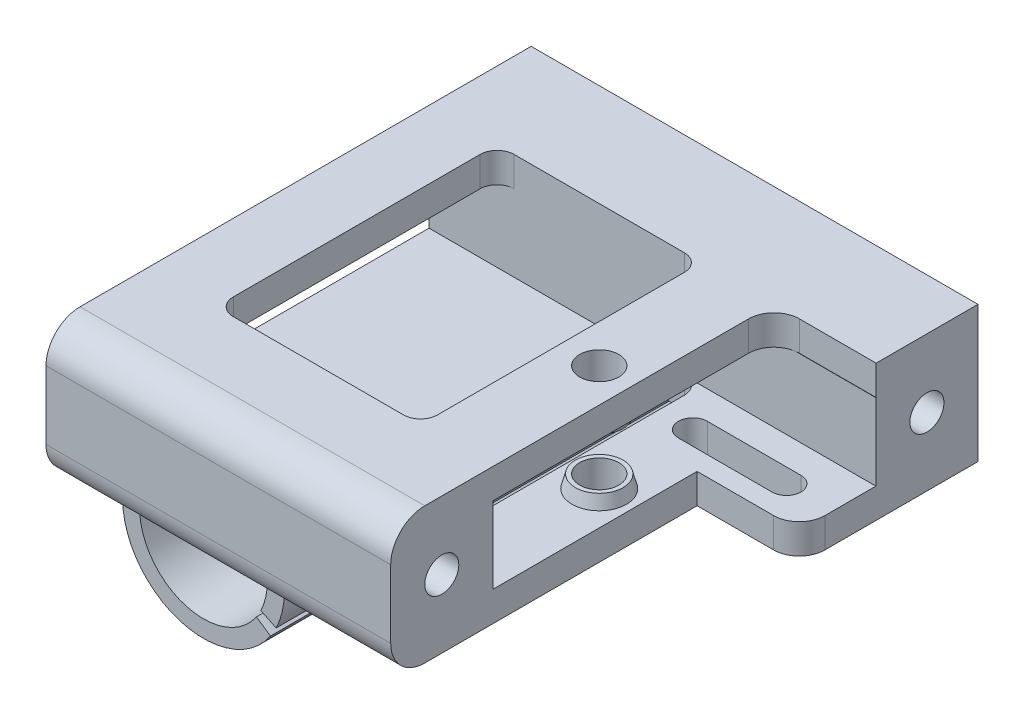
SolidWorks part; units mm, degrees
ref_plane "Front Plane" through (0, 0, 0) normal (0, 0, 1) x (1, 0, 0)
ref_plane "Top Plane" through (0, 0, 0) normal (0, 1, 0) x (1, 0, 0)
ref_plane "Right Plane" through (0, 0, 0) normal (1, 0, 0) x (0, 0, -1)
sketch "Sketch1" plane through (0, 0, 0) normal (0, 0, 1) x (1, 0, 0)
  line L0 (0, 0) -> (0, -31.5)
  line L1 (0, -31.5) -> (19, -31.5)
  line L2 (19, -31.5) -> (19, -16)
  line L3 (19, -16) -> (52.5, -16)
  line L4 (52.5, -16) -> (52.5, 0)
  line L5 (52.5, 0) -> (0, 0)
  line L6 (0, 0) -> (0.6966, -0.1385)
  dimension "D1" = 31.5
  dimension "D2" = 19
  dimension "D3" = 52.5
  dimension "D4" = 16
extrude "Boss-Extrude1" add sketch "Sketch1" along normal blind 57 contours L4 L5 L0 L1 L2 L3 region at (21.9019, -12.0885, 0)
ref_plane "Plane1" through (0, 0, 50) normal (0, 0, 1) x (1, 0, 0)
sketch "Sketch3" plane through (0, 0, 0) normal (-1, 0, 0) x (0, 0, 1)
  line L0 (57, 0) -> (0, 0) construction
  line L1 (12, -3.5) -> (45, -3.5)
  line L2 (12, -3.5) -> (12, -12.5)
  line L3 (12, -12.5) -> (45, -12.5)
  line L4 (45, -3.5) -> (45, -12.5)
  line L5 (57, -31.5) -> (48, -31.5)
  line L6 (57, -31.5) -> (57, -16)
  line L7 (57, -16) -> (48, -16)
  line L8 (48, -31.5) -> (48, -16)
  line L9 (0, 0) -> (0, -31.5) construction
  line L14 (57, -31.5) -> (0, -31.5) construction
  dimension "D1" = 9
  dimension "D2" = 33
  dimension "D3" = 3.5
  dimension "D4" = 12
  dimension "D5" = 15.5
  dimension "D6" = 9
extrude "Cut-Extrude2" cut sketch "Sketch3" against normal through all
fillet "Fillet1" radius 4 2 edges at (26.25, 0, 57) (26.25, -16, 57)
sketch "Sketch4" plane through (0, 0, 0) normal (0, 0, -1) x (-1, 0, 0)
  line L0 (-9.5, -22) -> (-9.5, -31.5) construction
  line L1 (0, -31.5) -> (-19, -31.5) construction
  line L2 (-15.7178, -26.1939) -> (-17.3759, -27.3123)
  line L3 (0, -31.5) -> (-19, -31.5)
  line L4 (0, -31.5) -> (0, -16)
  line L5 (0, -16) -> (-19, -16)
  line L6 (-19, -31.5) -> (-19, -16)
  line L7 (-16.241, -25.2878) -> (-18.0385, -26.1645)
  line L8 (-16.241, -25.2878) -> (-9.5, -22) construction
  circle A0 centre (-9.5, -22) radius 7.5
  circle A1 centre (-9.5, -22) radius 9.5
  line M8 (-19, -31.5) -> (0, -31.5)
  line M9 (0, -31.5) -> (0, 0)
  dimension "D1" = 15
  dimension "D2" = 19
  dimension "D3" = 8
  dimension "D4" = 64
extrude "Cut-Extrude3" cut sketch "Sketch4" against normal through all contours L5 A0 | L5 A0 | A1 L6 M8 | A1 L3 M9 | L7 A1 L2 A0 region at (16.8892, -26.2661, 0) region at (9.5, -22.3626, 0) region at (16.878, -29.378, 0) region at (2.122, -29.378, 0) region at (9.5, -15.3945, 0)
sketch "Sketch5" plane through (0, -16, 0) normal (0, -1, 0) x (1, 0, 0)
  line L0 (32, 28.5) -> (36, 28.5) construction
  line L1 (22, 45) -> (30, 45)
  line L2 (20, 43) -> (20, 14)
  line L3 (22, 12) -> (30, 12)
  line L4 (32, 43) -> (32, 14)
  line L5 (36, 17) -> (47, 17) construction
  line L6 (36, 18.7) -> (47, 18.7)
  line L7 (36, 15.3) -> (47, 15.3)
  line L8 (19, 48) -> (19, 0) construction
  line L9 (36, 28.5) -> (36, 17) construction
  line L10 (19, 0) -> (52.5, 0) construction
  line L11 (52.5, 0) -> (52.5, 18) construction
  line L12 (52.5, 53) -> (52.5, 0) construction
  line L14 (49.5, 18) -> (49.5, 21) construction
  line L15 (49.5, 21) -> (40.5, 21)
  line L16 (40.5, 21) -> (40.5, 57)
  line L17 (0, 57) -> (52.5, 57) construction
  line L18 (40.5, 57) -> (52.5, 57)
  line L19 (52.5, 57) -> (52.5, 18)
  arc A0 (20, 14) -> (22, 12) centre (22, 14) ccw
  arc A1 (30, 12) -> (32, 14) centre (30, 14) ccw
  arc A2 (32, 43) -> (30, 45) centre (30, 43) ccw
  arc A3 (22, 45) -> (20, 43) centre (22, 43) ccw
  circle A4 centre (36, 28.5) radius 2 construction
  arc A5 (36, 18.7) -> (36, 15.3) centre (36, 17) ccw
  arc A6 (47, 15.3) -> (47, 18.7) centre (47, 17) ccw
  arc A7 (52.5, 18) -> (49.5, 21) centre (49.5, 18) ccw
  point P17 (41.5, 17)
  line M7 (52.5, 53) -> (14, 53)
  line M12 (52.5, 0) -> (52.5, 53)
  dimension "D1" = 2
  dimension "D4" = 4
  dimension "D6" = 1.7
  dimension "D9" = 11.5
  dimension "D12" = 6
  dimension "D2" = 12
  dimension "D3" = 33
  dimension "D5" = 4
  dimension "D7" = 11
  dimension "D8" = 1
  dimension "D10" = 12
  dimension "D11" = 18
  dimension "D13" = 9
extrude "Cut-Extrude4" cut sketch "Sketch5" against normal up to surface (12.5 mm away) contours A4 | L7 A6 L6 A5 | A7 L16 L15 M12 M7 | L19 L18 L16 M7 | L2 A0 L3 A1 L4 A2 L1 A3 region at (41.5, -16, 17) region at (46.5267, -16, 36.9166) region at (46.5, -16, 55) up to face at (26.25, -3.5, 28.5)
sketch "Sketch6" plane through (0, 0, 0) normal (0, 1, 0) x (1, 0, 0)
  line L0 (52.5, 0) -> (0, 0) construction
  line L1 (10, -12) -> (30, -12)
  line L2 (8, -14) -> (8, -43)
  line L3 (10, -45) -> (30, -45)
  line L4 (32, -14) -> (32, -43)
  line L5 (0, -53) -> (0, 0) construction
  line L6 (52.5, -56.9686) -> (40.5, -56.9686) construction
  line L7 (43.5, -11.9686) -> (52.5, -11.9686)
  line L8 (40.5, -14.9686) -> (40.5, -56.9686)
  line L9 (40.5, -56.9686) -> (52.5, -56.9686)
  line L10 (52.5, -11.9686) -> (52.5, -56.9686)
  line L11 (52.5, -53) -> (52.5, 0) construction
  line L12 (36, -28.5) -> (32, -28.5) construction
  arc A0 (10, -45) -> (8, -43) centre (10, -43) cw
  arc A1 (32, -43) -> (30, -45) centre (30, -43) cw
  arc A2 (32, -14) -> (30, -12) centre (30, -14) ccw
  arc A3 (10, -12) -> (8, -14) centre (10, -14) ccw
  arc A4 (43.5, -11.9686) -> (40.5, -14.9686) centre (43.5, -14.9686) ccw
  circle A5 centre (36, -28.5) radius 2 construction
  point P6 (8, -45)
  point P11 (32, -12)
  point P14 (8, -12)
  point P25 (40.5, -11.9686)
  dimension "D3" = 2
  dimension "D8" = 3
  dimension "D9" = 4
  dimension "D10" = 4
  dimension "D1" = 33
  dimension "D2" = 24
  dimension "D4" = 12
  dimension "D5" = 8
  dimension "D6" = 45
  dimension "D7" = 12
extrude "Cut-Extrude5" cut sketch "Sketch6" against normal up to surface (3.5 mm away) up to face at (31, -3.5, 37.9895)
sketch "Sketch9" plane through (0, -3.5, 0) normal (0, -1, 0) x (1, 0, 0)
  line L0 (40.5, 21) -> (40.5, 53) construction
  line L1 (19, 0) -> (52.5, 0) construction
  circle A0 centre (36.5, 28.5) radius 3.2
  dimension "D1" = 6.4
  dimension "D2" = 4
  dimension "D3" = 28.5
ref_plane "Plane3" through (0, -5, 0) normal (0, -1, 0) x (-1, 0, 0)
sketch "Sketch10" plane through (0, -5, 0) normal (0, -1, 0) x (-1, 0, 0)
  circle A0 centre (-36.5, -28.5) radius 2.8
  dimension "D1" = 5.6
loft "Loft1" add profiles "Sketch9", "Sketch10" connector at (36.5, -3.5, 25.3) connector at (36.5, -5, 25.7)
ref_plane "Plane4" through (0, -8, 0) normal (0, -1, 0) x (-1, 0, 0)
mirror "Mirror2" about plane through (0, -8, 0) normal (0, -1, 0) of "Loft1"
sketch "Sketch11" plane through (0, -11, 0) normal (0, 1, 0) x (1, 0, 0)
  circle A0 centre (36.5, -28.5) radius 2.3
  dimension "D1" = 4.6
extrude "Cut-Extrude6" cut sketch "Sketch11" against normal through all both and the other way through all
sketch "Sketch13" plane through (52.5, 0, 0) normal (1, 0, 0) x (0, 0, -1)
  line L0 (-51, -8) -> (-6, -8) construction
  line L1 (-6, -8) -> (0, -8) construction
  line L2 (0, -16) -> (0, 0) construction
  line L3 (-51, -8) -> (-57, -8) construction
  line L5 (-57, -4) -> (-57, -12) construction
  circle A0 centre (-6, -8) radius 2
  circle A1 centre (-51, -8) radius 2
  dimension "D1" = 45
  dimension "D2" = 4
extrude "Cut-Extrude7" cut sketch "Sketch13" against normal blind 20
